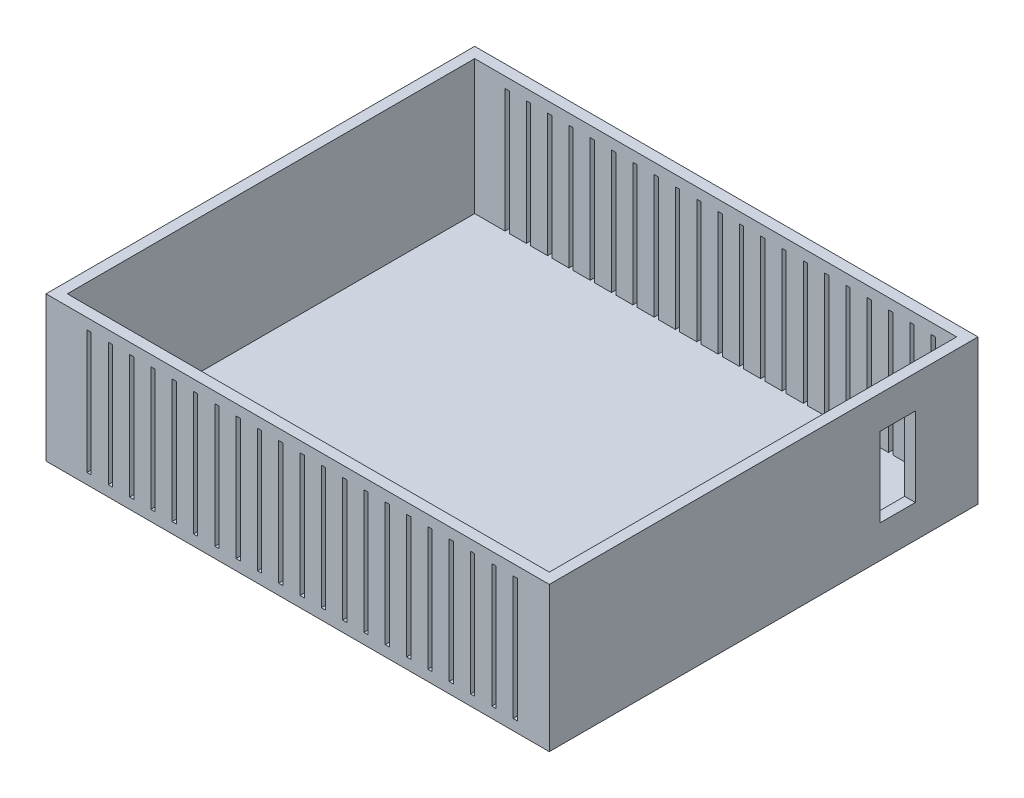
SolidWorks part; units mm, degrees
ref_plane "Front Plane" through (0, 0, 0) normal (0, 0, 1) x (1, 0, 0)
ref_plane "Top Plane" through (0, 0, 0) normal (0, 1, 0) x (1, 0, 0)
ref_plane "Right Plane" through (0, 0, 0) normal (1, 0, 0) x (0, 0, -1)
sketch "Sketch1" plane through (0, 0, 0) normal (0, 1, 0) x (1, 0, 0)
  line L0 (-143.65, -121.412) -> (-143.65, 121.412)
  line L1 (150, -127.762) -> (-150, -127.762)
  line L2 (150, -127.762) -> (150, 127.762)
  line L3 (150, 127.762) -> (-150, 127.762)
  line L4 (-150, -127.762) -> (-150, 127.762)
  line L5 (150, -127.762) -> (-150, 127.762) construction
  line L6 (150, 127.762) -> (-150, -127.762) construction
  line L7 (143.65, 121.412) -> (-143.65, 121.412)
  line L8 (143.65, -121.412) -> (143.65, 121.412)
  line L9 (143.65, -121.412) -> (-143.65, -121.412)
  point P0 (0, 0)
  point P10 (0, 0)
  dimension "D1" = 300
  dimension "D2" = 6.35
  dimension "D3" = 255.524
extrude "Boss-Extrude1" add sketch "Sketch1" along normal blind 80
sketch "Sketch2" plane through (0, 0, 0) normal (0, -1, 0) x (1, 0, 0)
  line L0 (150, -127.762) -> (-150, -127.762) construction
  line L1 (150, 127.762) -> (150, -127.762) construction
  line L2 (-150, 127.762) -> (150, 127.762) construction
  line L3 (-150, -127.762) -> (-150, 127.762) construction
  line L4 (150, -127.762) -> (-150, -127.762)
  line L5 (150, 127.762) -> (150, -127.762)
  line L6 (-150, 127.762) -> (150, 127.762)
  line L7 (-150, -127.762) -> (-150, 127.762)
extrude "Boss-Extrude2" add sketch "Sketch2" along normal blind 6.35
sketch "Sketch4" plane through (150, 0, 0) normal (1, 0, 0) x (0, 0, -1)
  line L0 (127.762, 80) -> (127.762, -6.35) construction
  line L1 (90.4032, 60.45) -> (69.3532, 60.45)
  line L2 (90.4032, 60.45) -> (90.4032, 13.2)
  line L3 (90.4032, 13.2) -> (69.3532, 13.2)
  line L4 (69.3532, 60.45) -> (69.3532, 13.2)
  line L5 (90.4032, 60.45) -> (69.3532, 13.2) construction
  line L6 (90.4032, 13.2) -> (69.3532, 60.45) construction
  point P0 (79.8782, 36.825)
  point P5 (0, 0)
  point P8 (127.762, 36.825)
  dimension "D1" = 47.25
  dimension "D2" = 21.05
extrude "Cut-Extrude1" cut sketch "Sketch4" against normal up to surface (6.35 mm away) up to face at (143.65, 40, 0)
sketch "Sketch5" plane through (0, 0, -127.762) normal (0, 0, -1) x (-1, 0, 0)
  line L0 (-143.65, 73.65) -> (143.65, 73.65)
  line L1 (-130.95, 73.65) -> (-130.95, 0)
  line L2 (-128.41, 73.65) -> (-128.41, 0)
  line L4 (-143.65, 0) -> (143.65, 0)
  line L5 (143.65, 0) -> (143.65, 80)
  line L6 (143.65, 80) -> (-143.65, 80)
  line L7 (-143.65, 80) -> (-143.65, 0)
  line L8 (-143.65, 0) -> (143.65, 0)
  line L9 (143.65, 0) -> (143.65, 80)
  line L10 (143.65, 80) -> (-143.65, 80)
  line L11 (-143.65, 80) -> (-143.65, 0)
  dimension "D2" = 6.35
  dimension "D3" = 2.54
  dimension "D4" = 12.7
  dimension "D1" = 0
extrude "Boss-Extrude4" add sketch "Sketch5" against normal blind 324.866 separate body contours L1 L8 L2 L0 region at (129.68, 36.825, -127.762)
pattern_linear "LPattern2" count 21 spacing 12.7 along (-1, 0, 0) of "Boss-Extrude4"
combine bodies "Combine2" operation type subtract main body 104 bodies to subtract 206 105 196 197 199 198 200 201 202 203 205 204 207 208 210 211 214 215 213 212 209
